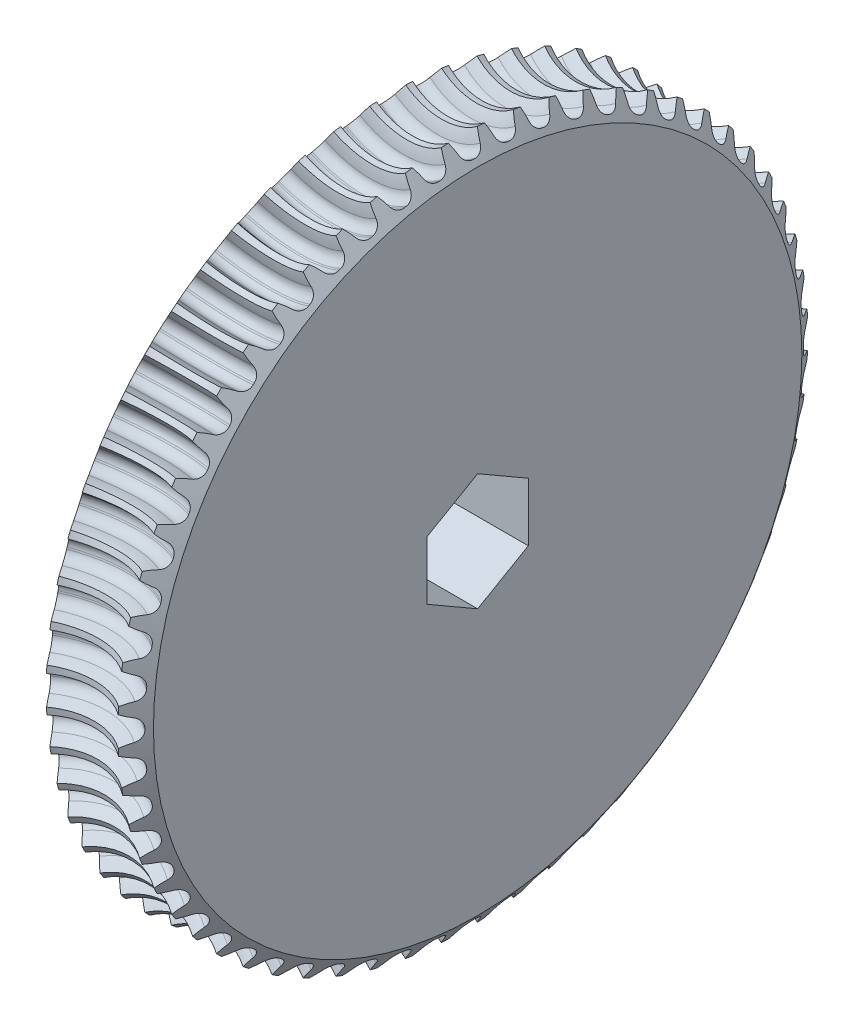
SolidWorks part; units mm, degrees
ref_plane "Piano frontale" through (0, 0, 0) normal (0, 0, 1) x (1, 0, 0)
ref_plane "Piano superiore" through (0, 0, 0) normal (0, 1, 0) x (1, 0, 0)
ref_plane "Piano destro" through (0, 0, 0) normal (1, 0, 0) x (0, 0, -1)
sketch "Schizzo1" plane through (0, 0, 0) normal (0, 0, 1) x (1, 0, 0)
  line L0 (-2.5, 0) -> (2.5, 0)
  line L1 (2.5, 0) -> (2.5, 16)
  line L3 (-2.5, 16) -> (-2.5, 0)
  line L4 (0.0015, 15.9453) -> (0.0015, 16.4453) construction
  line L5 (1.77, 17.022) -> (2.5, 16)
  line L6 (-1.769, 17.0235) -> (-2.5, 16)
  arc A0 (2.0606, 16.6151) -> (-2.0596, 16.6166) centre (0.0015, 19.4453) ccw construction
  arc A1 (-1.769, 17.0235) -> (1.77, 17.022) centre (0.0015, 19.4453) ccw
  dimension "D1" = 7
  dimension "D5" = 0.5
  dimension "D6" = 16
  dimension "D2" = 5
  dimension "D3" = 2.5
  dimension "D4" = 5
revolve "Rivoluzione1" add sketch "Schizzo1" angle 360 mid plane about L0
sketch "Schizzo2" plane through (0, 0, 0) normal (1, 0, 0) x (0, 0, -1)
  line L0 (0, 19.4453) -> (25.188, 19.4453) construction
  line L1 (0, 0) -> (0.5758, 16.4899) construction
  line L2 (0, 16) -> (0, 0) construction
  line L3 (0, 0) -> (0, 16.5) construction
  line L4 (0.5584, 15.9903) -> (4.3663, 14.8723) construction
  line L5 (1.5307, 17.6489) -> (-1.5307, 17.6489)
  line L6 (-0.4466, 15.4936) -> (0.4466, 15.4936)
  circle A0 centre (0, 0) radius 16
  circle A1 centre (0, 0) radius 16.5
  circle A2 centre (0, 0) radius 15.5
  arc A4 (-1.5307, 17.6489) -> (-0.4466, 15.4936) centre (-4.3663, 14.8723) cw
  arc A5 (1.5307, 17.6489) -> (0.4466, 15.4936) centre (4.3663, 14.8723) ccw
  dimension "D1" = 32
  dimension "D4" = 2
  dimension "D2" = 0.5
  dimension "D3" = 0.5
revolve "Taglia-Rivoluzione1" cut sketch "Schizzo2" angle 360 about L0
fillet "Raccordo2" radius 0.5 2 edges at (0, 15.4936, -0.4466) (0, 15.4936, 0.4466)
pattern_circular "RipetizioneCircolare1" count 60 every 6 about axis through (1.77, 0, 0) along (-1, 0, 0) of "Raccordo2", "Taglia-Rivoluzione1"
sketch "Schizzo3" plane through (0, 0, 0) normal (1, 0, 0) x (0, 0, -1)
  line L1 (0, 2.8868) -> (-2.5, 1.4434)
  line L2 (-2.5, 1.4434) -> (-2.5, -1.4434)
  line L3 (-2.5, -1.4434) -> (0, -2.8868)
  line L4 (0, -2.8868) -> (2.5, -1.4434)
  line L5 (2.5, -1.4434) -> (2.5, 1.4434)
  line L6 (2.5, 1.4434) -> (0, 2.8868)
  circle A0 centre (0, 0) radius 2.5 construction
  dimension "D1" = 2.5
extrude "Taglio-Estrusione1" cut sketch "Schizzo3" against normal through all both and the other way through all
